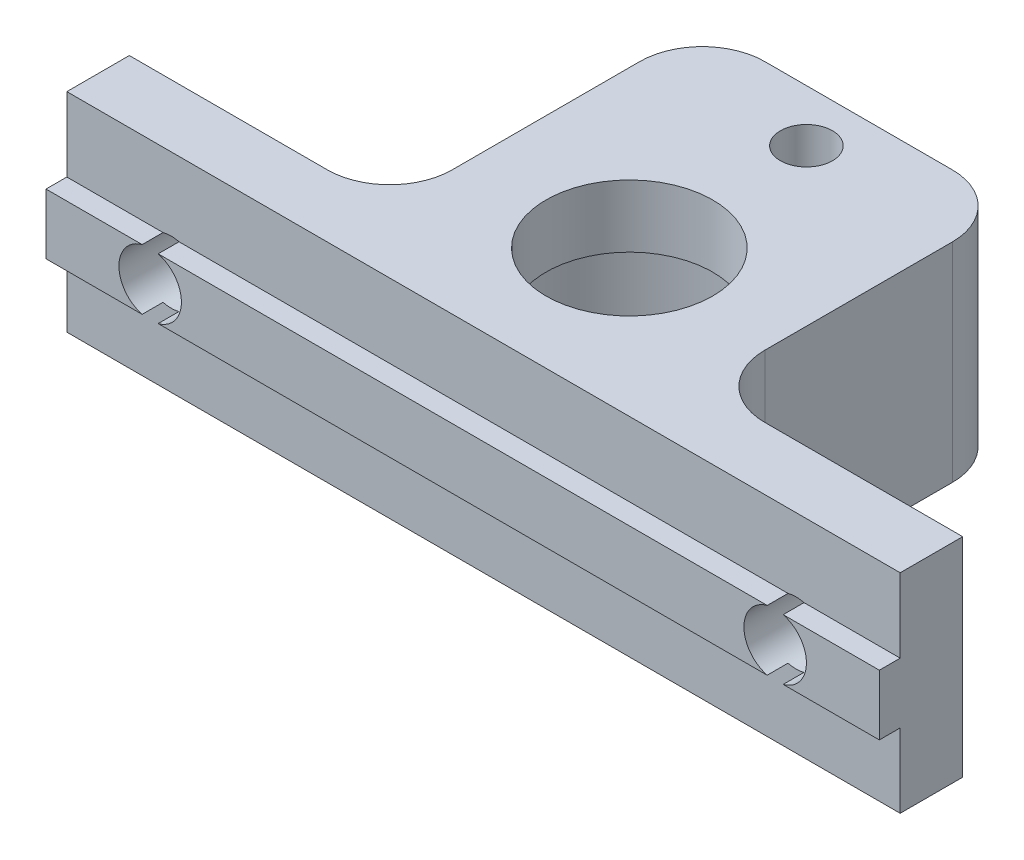
SolidWorks part; units mm, degrees
ref_plane "Front Plane" through (0, 0, 0) normal (0, 0, 1) x (1, 0, 0)
ref_plane "Top Plane" through (0, 0, 0) normal (0, 1, 0) x (1, 0, 0)
ref_plane "Right Plane" through (0, 0, 0) normal (1, 0, 0) x (0, 0, -1)
sketch "Esquisse1" plane through (0, 0, 0) normal (0, 0, 1) x (1, 0, 0)
  line L1 (-20, 0) -> (20, 0)
  line L2 (-20, 0) -> (-20, 10)
  line L3 (-20, 10) -> (20, 10)
  line L4 (20, 0) -> (20, 10)
  point P5 (0, 0)
  point P6 (0, 0)
  dimension "D1" = 40
  dimension "D2" = 10
extrude "Main" add sketch "Esquisse1" along normal blind 3
sketch "Esquisse2" plane through (0, 0, 3) normal (0, 0, 1) x (1, 0, 0)
  line L0 (20, 0) -> (20, 10) construction
  line L1 (20, 3.55) -> (-20, 3.55)
  line L2 (20, 3.55) -> (20, 6.45)
  line L3 (20, 6.45) -> (-20, 6.45)
  line L4 (-20, 3.55) -> (-20, 6.45)
  line L5 (-20, 10) -> (-20, 0) construction
  point P8 (-20, 5)
  point P9 (-20, 5)
  dimension "D1" = 2.9
extrude "MakerBeamRail" add sketch "Esquisse2" along normal blind 1
sketch "Esquisse3" plane through (0, 0, 0) normal (0, 0, -1) x (-1, 0, 0)
  line L0 (-20, 0) -> (-20, 10) construction
  circle A0 centre (-15, 5) radius 1.5
  point P5 (-20, 5)
  dimension "D1" = 3
  dimension "D2" = 5
extrude "MakerBeamHole" cut sketch "Esquisse3" against normal through all
pattern_linear "Répétition linéaire1" count 2 spacing 30 along (-1, 0, 0) of "MakerBeamHole"
sketch "Sketch3" plane through (0, 0, 0) normal (0, 1, 0) x (1, 0, 0)
  line L0 (20, 0) -> (-20, 0) construction
  line L1 (-7.5, 0) -> (7.5, 0)
  line L2 (-7.5, 0) -> (-7.5, 15)
  line L3 (-7.5, 15) -> (7.5, 15)
  line L4 (7.5, 0) -> (7.5, 15)
  point P7 (0, 15)
  dimension "D1" = 15
  dimension "D2" = 15
extrude "MagnetSupport" add sketch "Sketch3" along normal blind 10
fillet "Fillet5" radius 3 4 edges at (7.5, 5, 0) (-7.5, 5, 0) (-7.5, 5, -15) (7.5, 5, -15)
sketch "Sketch4" plane through (0, 0, 0) normal (0, -1, 0) x (1, 0, 0)
  line L0 (-14.6159, 3) -> (14.6159, 3) construction
  circle A0 centre (0, -4) radius 6.25
  point P2 (0, 0)
  dimension "D1" = 12.5
  dimension "D2" = 7
extrude "MagnetBigHole" cut sketch "Sketch4" against normal blind 7
sketch "Sketch5" plane through (0, 7, 0) normal (0, -1, 0) x (1, 0, 0)
  circle A0 centre (0, -4) radius 4
  circle A1 centre (0, -4) radius 6.25 construction
  dimension "D1" = 8
extrude "MagnetSmallHole" cut sketch "Sketch5" against normal through all
sketch "Sketch6" plane through (0, 10, 0) normal (0, 1, 0) x (1, 0, 0)
  line L0 (14.6159, -3) -> (-14.6159, -3) construction
  circle A0 centre (0, 12.5) radius 1.25
  point P2 (0, 0)
  dimension "D1" = 2.5
  dimension "D2" = 15.5
extrude "SubMagnetFixHole" cut sketch "Sketch6" against normal through all
